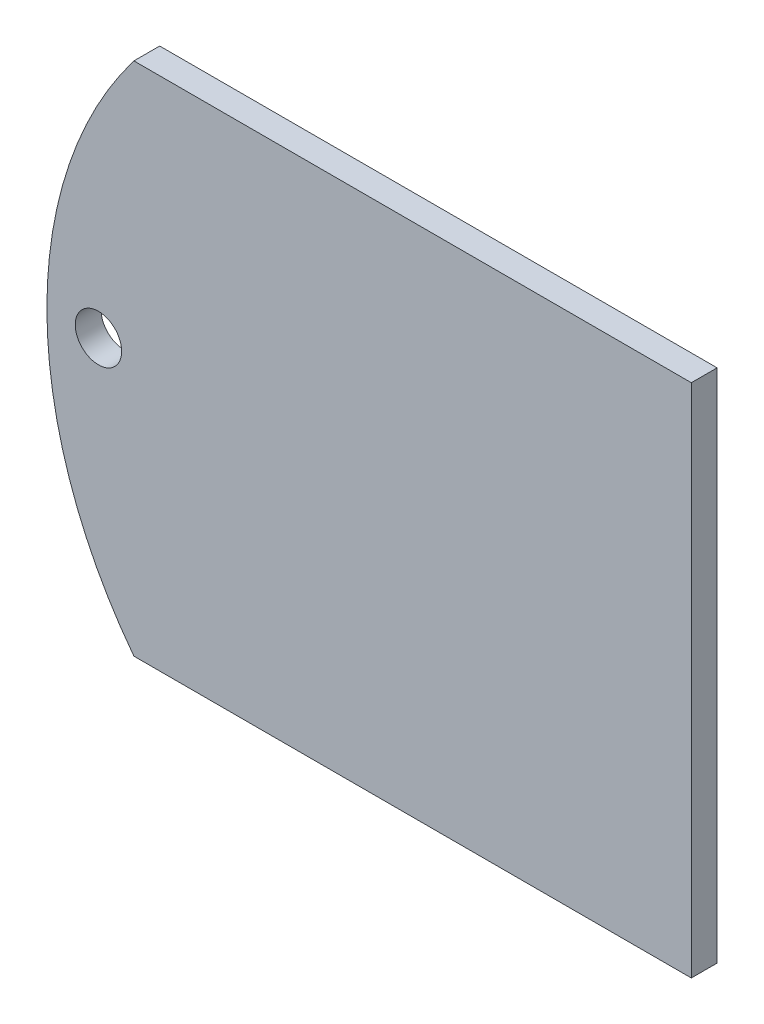
SolidWorks part; units mm, degrees
material "ABS"
ref_plane "Alzado" through (0, 0, 0) normal (0, 0, 1) x (1, 0, 0)
ref_plane "Planta" through (0, 0, 0) normal (0, 1, 0) x (1, 0, 0)
ref_plane "Vista lateral" through (0, 0, 0) normal (1, 0, 0) x (0, 0, -1)
sketch "Croquis1" plane through (0, 0, 0) normal (0, 0, 1) x (1, 0, 0)
  line L0 (-33, -20) -> (-33, 20) construction
  line L1 (0, 0) -> (0, 22.8374) construction
  line L2 (-26.2488, -20) -> (17, -20)
  line L3 (17, -20) -> (17, 20)
  line L4 (17, 20) -> (-33, 20)
  arc A0 (-26.2488, 20) -> (-26.2488, -20) centre (0, 0) ccw
  circle A1 centre (-29, 0) radius 1.8
  circle A2 centre (0, 0) radius 29 construction
  dimension "D1" = 66
  dimension "D5" = 4
  dimension "D6" = 3.6
  dimension "D2" = 20
  dimension "D3" = 20
  dimension "D4" = 50
extrude "Saliente-Extruir1" add sketch "Croquis1" along normal blind 2 contours L4 A0 L2 L3 region at (-6.8483, 0, 0)
